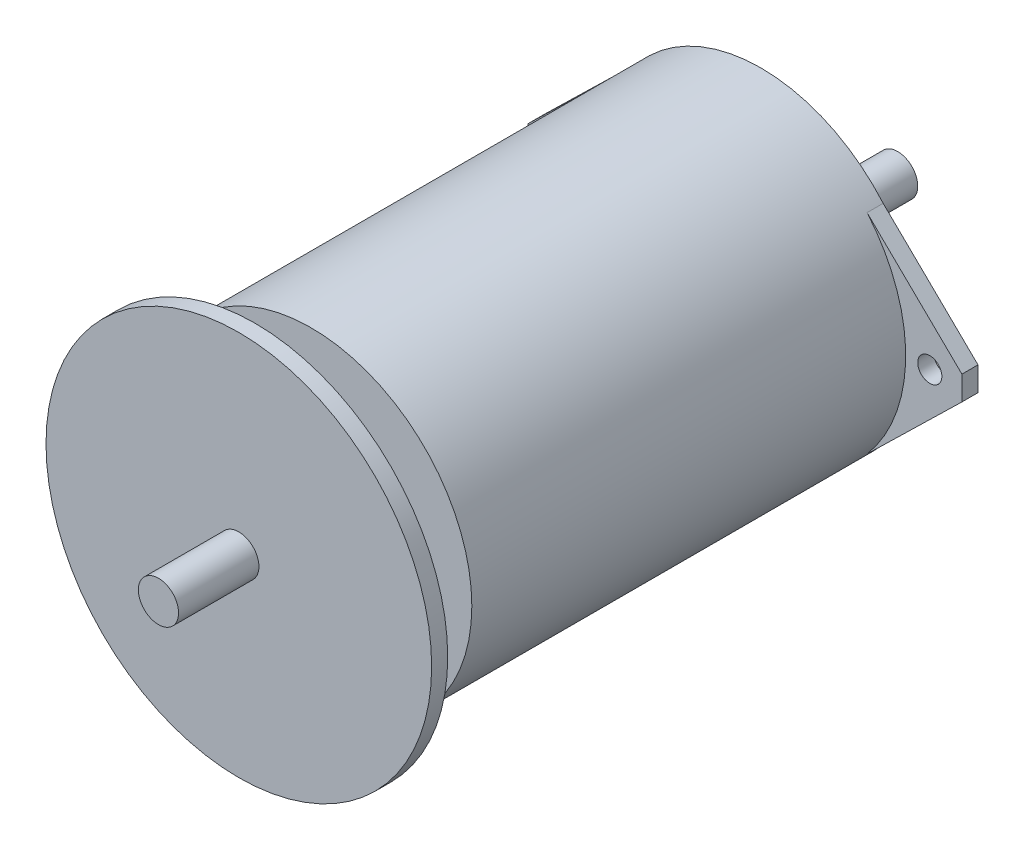
SolidWorks part; units mm, degrees
ref_plane "Front Plane" through (0, 0, 0) normal (0, 0, 1) x (1, 0, 0)
ref_plane "Top Plane" through (0, 0, 0) normal (0, 1, 0) x (1, 0, 0)
ref_plane "Right Plane" through (0, 0, 0) normal (1, 0, 0) x (0, 0, -1)
sketch "Sketch1" plane through (0, 0, 0) normal (0, 0, 1) x (1, 0, 0)
  line L0 (-71.2118, 21.3991) -> (-71.2118, 24.3985)
  line L1 (-17.2124, 21.3991) -> (-31.6015, 7.3754)
  line L2 (-17.2124, 24.3985) -> (-31.6015, 38.4221)
  line L3 (-71.2118, 24.3985) -> (-56.8227, 38.4221)
  line L4 (-71.2118, 21.3991) -> (-56.8227, 7.3754)
  line L5 (-17.2124, 24.3985) -> (-17.2124, 21.3991)
  line L6 (-44.2121, 22.8988) -> (-56.8227, 38.4221) construction
  line L7 (-44.2121, 22.8988) -> (-21.2121, 22.8988) construction
  circle A0 centre (-44.2121, 22.8988) radius 20
  circle A1 centre (-21.2121, 22.8988) radius 1.5
  circle A2 centre (-67.2121, 22.8988) radius 1.5
  circle A3 centre (-44.2121, 22.8988) radius 9
  circle A4 centre (-44.2121, 22.8988) radius 2.5
  dimension "D1" = 2
  dimension "D3" = 2
  dimension "D2" = 20
  dimension "D4" = 23
extrude "Boss-Extrude2" add sketch "Sketch1" along normal blind 56 contours A0
extrude "Boss-Extrude3" add sketch "Sketch1<4>" along normal blind 2 contours A0 L1 L5 L2 | A0 L3 L0 L4 region at (-70.9262, 22.8988, 0) region at (-25.1842, 15.867, 0)
sketch "Sketch1<4>" plane through (0, 0, 0) normal (0, 0, 1) x (1, 0, 0) same geometry as "Sketch1"
extrude "Boss-Extrude4" add sketch "Sketch1<5>" against normal blind 4 contours A3 region at (-52.9576, 22.8988, 0)
sketch "Sketch1<5>" plane through (0, 0, 0) normal (0, 0, 1) x (1, 0, 0) same geometry as "Sketch1"
extrude "Boss-Extrude6" add sketch "Sketch1<7>" along normal blind 65 and the other way blind 17 contours A4 region at (-44.2121, 22.8988, 0)
sketch "Sketch1<7>" plane through (0, 0, 0) normal (0, 0, 1) x (1, 0, 0) same geometry as "Sketch1"
sketch "Sketch8" plane through (0, 0, 65) normal (0, 0, 1) x (1, 0, 0)
  circle A0 centre (-44.2121, 22.8988) radius 24
  circle A2 centre (-44.2121, 22.8988) radius 2.5
extrude "Boss-Extrude9" add sketch "Sketch8" against normal blind 2
sketch "Sketch9" plane through (0, 0, 65) normal (0, 0, 1) x (1, 0, 0)
  circle A0 centre (-44.2121, 22.8988) radius 2.5
extrude "Boss-Extrude11" add sketch "Sketch9" along normal blind 10
